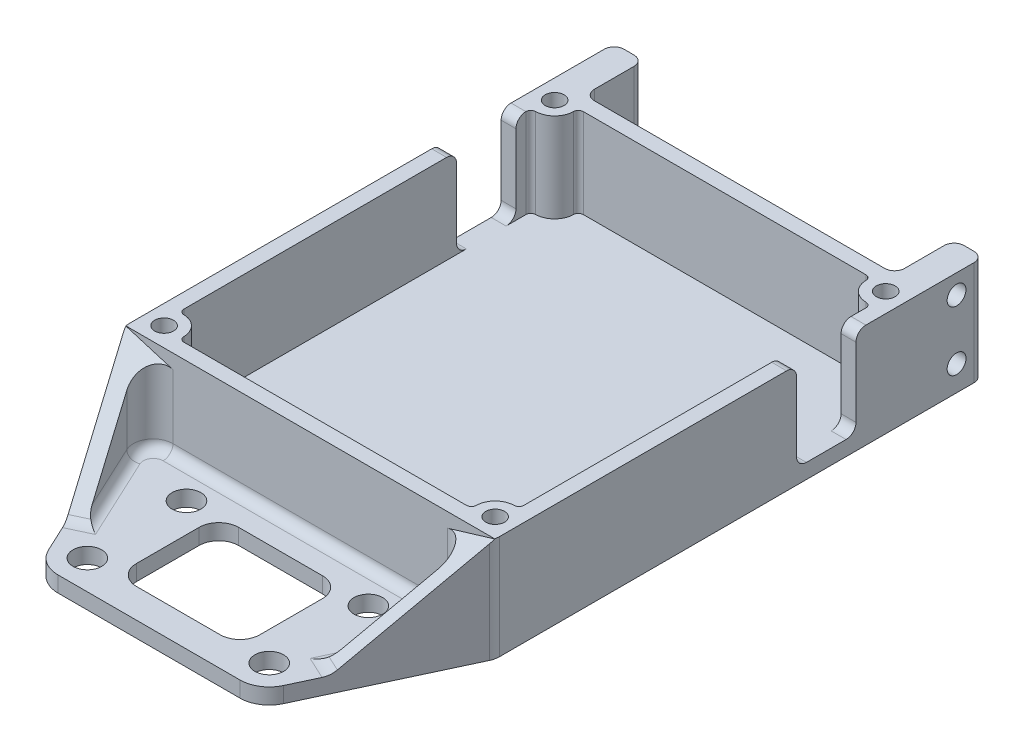
SolidWorks part; units mm, degrees
ref_plane "Front Plane" through (0, 0, 0) normal (0, 0, 1) x (1, 0, 0)
ref_plane "Top Plane" through (0, 0, 0) normal (0, 1, 0) x (1, 0, 0)
ref_plane "Right Plane" through (0, 0, 0) normal (1, 0, 0) x (0, 0, -1)
sketch "Sketch1" plane through (0, 0, 0) normal (0, 1, 0) x (1, 0, 0)
  line L0 (37.3, 43.3) -> (-37.3, 43.3)
  line L1 (29.5, -35.5) -> (-29.5, -35.5) construction
  line L2 (29.5, -35.5) -> (29.5, 35.5) construction
  line L3 (29.5, 35.5) -> (-29.5, 35.5) construction
  line L4 (-29.5, -35.5) -> (-29.5, 35.5) construction
  line L5 (29.5, -35.5) -> (-29.5, 35.5) construction
  line L6 (29.5, 35.5) -> (-29.5, -35.5) construction
  line L7 (-37.3, -43.3) -> (-37.3, 43.3)
  line L8 (37.3, -43.3) -> (-37.3, -43.3)
  line L9 (37.3, -43.3) -> (37.3, 43.3)
  line L10 (29.5, 35.5) -> (37.3, 43.3) construction
  circle A0 centre (33.4, 39.4) radius 1.9 construction
  circle A2 centre (33.4, 39.4) radius 3.9 construction
  point P0 (0, 0)
  dimension "D4" = 3.8
  dimension "D5" = 2
  dimension "D1" = 71
  dimension "D2" = 59
extrude "Boss-Extrude1" add sketch "Sketch1" along normal blind 21
shell "Shell1" thickness 3 removed face at (0, 21, 0)
sketch "Sketch2" plane through (0, 0, 0) normal (0, 1, 0) x (1, 0, 0)
  circle A8 centre (-18.35, -49.9375) radius 1.9 construction
  circle A9 centre (-18.35, -69.9375) radius 1.9 construction
  circle A10 centre (18.35, -69.9375) radius 1.9 construction
  circle A11 centre (18.35, -49.9375) radius 1.9 construction
  circle A12 centre (-18.35, -49.9375) radius 1.9
  circle A13 centre (-18.35, -69.9375) radius 1.9
  circle A14 centre (18.35, -69.9375) radius 1.9
  circle A15 centre (18.35, -49.9375) radius 1.9
sketch "Sketch3" plane through (0, 0, 0) normal (0, 1, 0) x (1, 0, 0)
  line L0 (-37.3, -43.3) -> (-23.6959, -72.4338)
  line L1 (37.3, -43.3) -> (23.6959, -72.4338)
  line L2 (-12.45, -69.9375) -> (-12.45, -49.3)
  line L3 (12.45, -69.9375) -> (12.45, -49.3)
  line L4 (12.45, -49.3) -> (-12.45, -49.3)
  line L5 (-12.45, -69.9375) -> (12.45, -69.9375)
  line L6 (-18.35, -75.8375) -> (18.35, -75.8375)
  line L7 (-37.3, -43.3) -> (37.3, -43.3) construction
  line L8 (-37.3, -43.3) -> (37.3, -43.3)
  circle A0 centre (-18.35, -69.9375) radius 2.9
  circle A1 centre (18.35, -69.9375) radius 2.9
  circle A2 centre (-18.35, -69.9375) radius 1.9 construction
  arc A3 (-23.6959, -72.4338) -> (-18.35, -75.8375) centre (-18.35, -69.9375) ccw
  arc A4 (18.35, -75.8375) -> (23.6959, -72.4338) centre (18.35, -69.9375) ccw
  circle A5 centre (18.35, -49.9375) radius 2.9
  circle A6 centre (-18.35, -49.9375) radius 2.9
  dimension "D1" = 1
  dimension "D2" = 3
  dimension "D3" = 6
extrude "Boss-Extrude2" add sketch "Sketch3" along normal blind 3.175
fillet "Fillet2" radius 4 4 edges at (12.45, 1.5875, 69.9375) (12.45, 1.5875, 49.3) (-12.45, 1.5875, 69.9375) (-12.45, 1.5875, 49.3)
sketch "Sketch4" plane through (47.2224, 0, 22.0507) normal (0.9061, 0, 0.4231) x (0.4231, 0, -0.9061)
  line L0 (-23.4519, 21) -> (-23.4519, 3.175) construction
  line L1 (-55.6054, 3.175) -> (-23.4519, 3.175) construction
  line L2 (-23.4519, 21) -> (-23.4519, 3.175)
  line L3 (-55.6054, 3.175) -> (-23.4519, 3.175)
  line L4 (-48.4519, 3.175) -> (-23.4519, 21)
  line M3 (-23.4519, 3.175) -> (-55.6054, 3.175)
  dimension "D1" = 25
extrude "Boss-Extrude3" add sketch "Sketch4" against normal blind 3 contours L4 L2 M3 region at (33.7742, 9.1167, 50.8507)
mirror "Mirror1" about plane through (0, 0, 0) normal (1, 0, 0) of "Boss-Extrude3"
fillet "Fillet3" radius 4 6 edges at (33.989, 11.5881, 43.3) (-33.989, 11.5881, 43.3) (-37.3, 10.5, -43.3) (37.3, 10.5, -43.3) (-37.3, 10.5, 43.3) (37.3, 10.5, 43.3)
fillet "Fillet4" radius 4 2 edges at (-25.3634, 3.175, 65.3174) (25.3634, 3.175, 65.3174)
fillet "Fillet5" radius 2 4 edges at (-34.3, 12, -40.3) (34.3, 12, -40.3) (-34.3, 12, 40.3) (34.3, 12, 40.3)
sketch "Sketch5" plane through (0, 0, 0) normal (1, 0, 0) x (0, 0, -1)
  line L1 (32.5, 23) -> (20.5, 23)
  line L2 (32.5, 23) -> (32.5, 3)
  line L3 (32.5, 3) -> (20.5, 3)
  line L4 (20.5, 23) -> (20.5, 3)
  line L5 (32.5, 23) -> (20.5, 3) construction
  line L6 (32.5, 3) -> (20.5, 23) construction
  line L8 (40.3, 3) -> (40.3, 21) construction
  line L9 (38.3, 3) -> (-38.3, 3) construction
  line L10 (38.3, 3) -> (-38.3, 3)
  circle A0 centre (26.5, 13) radius 6 construction
  point P0 (26.5, 13)
  point P11 (26.5, 11.9916)
  dimension "D2" = 12
  dimension "D1" = 13.8
  dimension "D3" = 10
extrude "Cut-Extrude1" cut sketch "Sketch5" against normal up to surface (37.3 mm away) contours L1 L4 L3 L2 region at (0, 13, -26.5) up to face at (-37.3, 10.5, 1.5561)
sketch "Sketch6" plane through (0, 0, 0) normal (1, 0, 0) x (0, 0, -1)
  line L1 (29.5, 3) -> (17.5, 3)
  line L2 (29.5, 3) -> (29.5, 17)
  line L3 (29.5, 17) -> (17.5, 17) construction
  line L4 (17.5, 3) -> (17.5, 17)
  line L5 (29.5, 3) -> (17.5, 17) construction
  line L6 (29.5, 17) -> (17.5, 3) construction
  line L7 (40.3, 21) -> (40.3, 3) construction
  line L8 (-38.3, 3) -> (38.3, 3) construction
  line L9 (-38.3, 3) -> (38.3, 3)
  line L10 (29.5, 17) -> (29.5, 21)
  line L11 (-42.4121, 21) -> (39.3, 21) construction
  line L12 (29.5, 21) -> (17.5, 21)
  line L13 (17.5, 21) -> (17.5, 17)
  point P0 (23.5, 10)
  dimension "D1" = 16.8
  dimension "D2" = 12
  dimension "D3" = 14
extrude "Cut-Extrude2" cut sketch "Sketch6" along normal up to surface (37.3 mm away) contours L12 L13 L4 L1 L2 L10 region at (0, 12, -23.5) up to face at (37.3, 10.5, 1.5561)
fillet "Fillet6" radius 2 8 edges at (-35.8, 21, -32.5) (-35.8, 21, -20.5) (-35.8, 3, -32.5) (-35.8, 3, -20.5) (35.8, 21, -29.5) (35.8, 21, -17.5) (35.8, 3, -29.5) (35.8, 3, -17.5)
sketch "Sketch7" plane through (0, 0, 0) normal (0, 1, 0) x (1, 0, 0)
  line L0 (-37.3, 39.3) -> (-37.3, 55.3)
  line L1 (37.3, 39.3) -> (37.3, 55.3)
  line L2 (37.3, 55.3) -> (31.3, 55.3)
  line L3 (31.3, 55.3) -> (31.3, 43.3)
  line L4 (33.3, 43.3) -> (-33.3, 43.3) construction
  line L5 (0, 0) -> (0, 40.3) construction
  line L6 (32.3, 40.3) -> (-32.3, 40.3) construction
  line L7 (-37.3, 55.3) -> (-31.3, 55.3)
  line L8 (-31.3, 55.3) -> (-31.3, 43.3)
  line L9 (33.3, 43.3) -> (-33.3, 43.3)
  arc A0 (37.3, 39.3) -> (33.3, 43.3) centre (33.3, 39.3) ccw construction
  arc A1 (-33.3, 43.3) -> (-37.3, 39.3) centre (-33.3, 39.3) ccw construction
  arc A2 (37.3, 39.3) -> (33.3, 43.3) centre (33.3, 39.3) ccw
  arc A3 (-33.3, 43.3) -> (-37.3, 39.3) centre (-33.3, 39.3) ccw
  dimension "D1" = 6
  dimension "D2" = 12
extrude "Boss-Extrude4" add sketch "Sketch7" along normal up to surface (21 mm away) contours A3 L9 L8 L7 L0 | A2 L1 L2 L3 L9 region at (34.3959, 0, -48.9862) region at (-34.3959, 0, -48.9862) up to face at (0, 21, -38.0738)
fillet "Fillet7" radius 2 6 edges at (37.3, 10.5, -55.3) (31.3, 10.5, -55.3) (-37.3, 10.5, -55.3) (-31.3, 10.5, -55.3) (31.3, 10.5, -43.3) (-31.3, 10.5, -43.3)
fillet "Fillet8" radius 2 5 edges at (-27.3968, 3.175, 57.4175) (-31.0808, 3.175, 45.1517) (0, 3.175, 43.3) (31.0808, 3.175, 45.1517) (27.3968, 3.175, 57.4175)
sketch "Sketch8" plane through (37.3, 0, 0) normal (1, 0, 0) x (0, 0, -1)
  circle A0 centre (49.8, 17.096) radius 2.5 construction
  circle A1 centre (49.8, 5.096) radius 2.5 construction
  circle A2 centre (49.8, 17.096) radius 2.5 construction
  circle A3 centre (49.8, 5.096) radius 2.5 construction
  circle A4 centre (49.8, 5.096) radius 1.9
  circle A5 centre (49.8, 17.096) radius 1.9
  dimension "D1" = 3.8
extrude "Cut-Extrude3" cut sketch "Sketch8" against normal blind 5
mirror "Mirror2" about plane through (0, 0, 0) normal (1, 0, 0) of "Cut-Extrude3"
sketch "Sketch9" plane through (0, 0, 0) normal (0, 1, 0) x (1, 0, 0)
  line L0 (0, 0) -> (0, 35.5) construction
  line L1 (29.5, 35.5) -> (-29.5, -35.5) construction
  line L2 (29.5, 35.5) -> (-29.5, 35.5) construction
  line L3 (0, 0) -> (-29.5, 0) construction
  line L4 (-29.5, -35.5) -> (-29.5, 35.5) construction
  circle A1 centre (33.4, 39.4) radius 3.9 construction
  circle A2 centre (33.4, 39.4) radius 3.9
  circle A3 centre (-33.4, 39.4) radius 3.9
  circle A4 centre (33.4, -39.4) radius 3.9
  circle A5 centre (-33.4, -39.4) radius 3.9
extrude "Boss-Extrude5" add sketch "Sketch9" along normal up to surface (21 mm away) up to face at (0, 21, 21.7882)
fillet "Fillet9" radius 1 8 edges at (34.3, 12, 35.6053) (29.6053, 12, 40.3) (-29.6053, 12, 40.3) (-34.3, 12, 35.6053) (34.3, 12, -35.6053) (29.6053, 12, -40.3) (-29.6053, 12, -40.3) (-34.3, 12, -35.6053)
ref_plane "Plane1" through (0, 11, 0) normal (0, 1, 0) x (1, 0, 0)
sketch "Sketch10" plane through (0, 21, 0) normal (0, 1, 0) x (1, 0, 0)
  circle A0 centre (33.4, 39.4) radius 1.9 construction
  circle A1 centre (33.4, 39.4) radius 1.9
  circle A2 centre (-33.4, 39.4) radius 1.9
  circle A3 centre (-33.4, -39.4) radius 1.9
  circle A4 centre (33.4, -39.4) radius 1.9
extrude "Cut-Extrude4" cut sketch "Sketch10" against normal up to surface (10 mm away) up to plane "Plane1"
